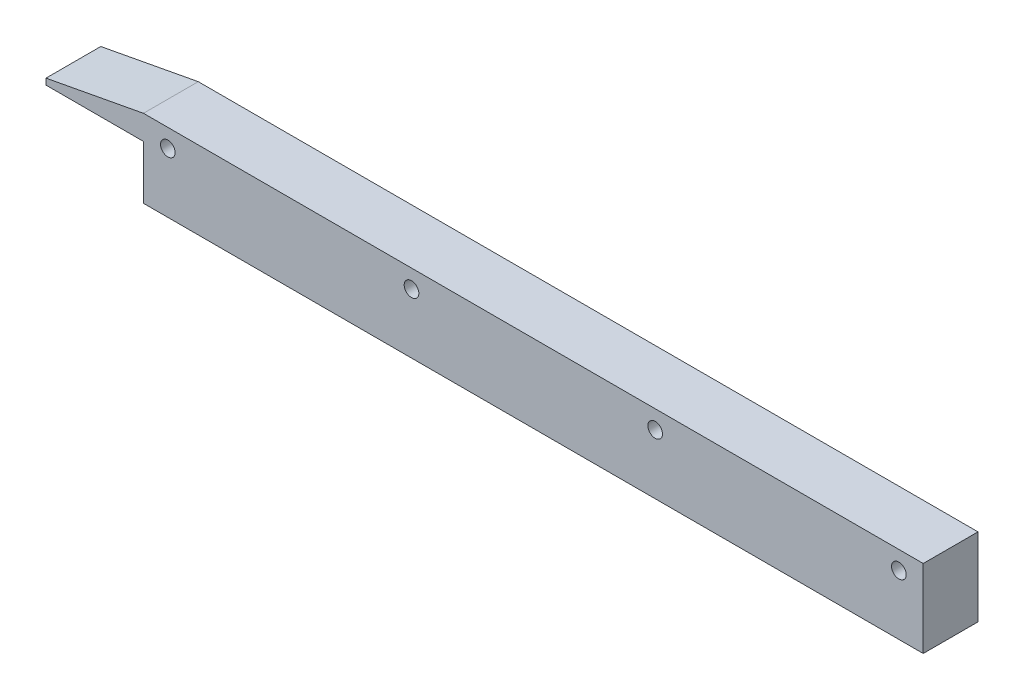
SolidWorks part; units mm, degrees
ref_plane "Front Plane" through (0, 0, 0) normal (0, 0, 1) x (1, 0, 0)
ref_plane "Top Plane" through (0, 0, 0) normal (0, 1, 0) x (1, 0, 0)
ref_plane "Right Plane" through (0, 0, 0) normal (1, 0, 0) x (0, 0, -1)
sketch "Sketch1" plane through (0, 0, 0) normal (0, 0, 1) x (1, 0, 0)
  line L0 (0, 12.7) -> (25.4, 12.7)
  line L5 (25.4, 12.7) -> (25.4, -1.27)
  line L6 (25.4, -1.27) -> (228.6, -1.27)
  line L7 (228.6, -1.27) -> (228.6, 19.05)
  line L12 (228.6, 19.05) -> (25.4, 19.05)
  line L13 (25.4, 19.05) -> (0, 14.2875)
  line L14 (0, 14.2875) -> (0, 12.7)
  dimension "D1" = 12.7
  dimension "D2" = 25.4
  dimension "D3" = 228.6
  dimension "D4" = 6.35
  dimension "D9" = 1.27
  dimension "D10" = 1.5875
extrude "Boss-Extrude1" add sketch "Sketch1" against normal up to surface (14.2752 mm away)
sketch "Sketch2" plane through (0, 0, 0) normal (0, 0, 1) x (1, 0, 0)
  line L0 (228.6, 19.05) -> (25.4, 19.05) construction
  line L1 (25.4, 12.7) -> (25.4, -1.27) construction
  line L2 (228.6, -1.27) -> (228.6, 19.05) construction
  circle A0 centre (31.75, 14.2875) radius 1.905
  circle A1 centre (95.25, 14.2875) radius 1.905
  circle A2 centre (158.75, 14.2875) radius 1.905
  circle A3 centre (222.25, 14.2875) radius 1.905
  dimension "D1" = 3.81
  dimension "D2" = 4.7625
  dimension "D3" = 6.35
  dimension "D5" = 6.35
  dimension "D4" = 4
extrude "Cut-Extrude2" cut sketch "Sketch2" against normal through all
